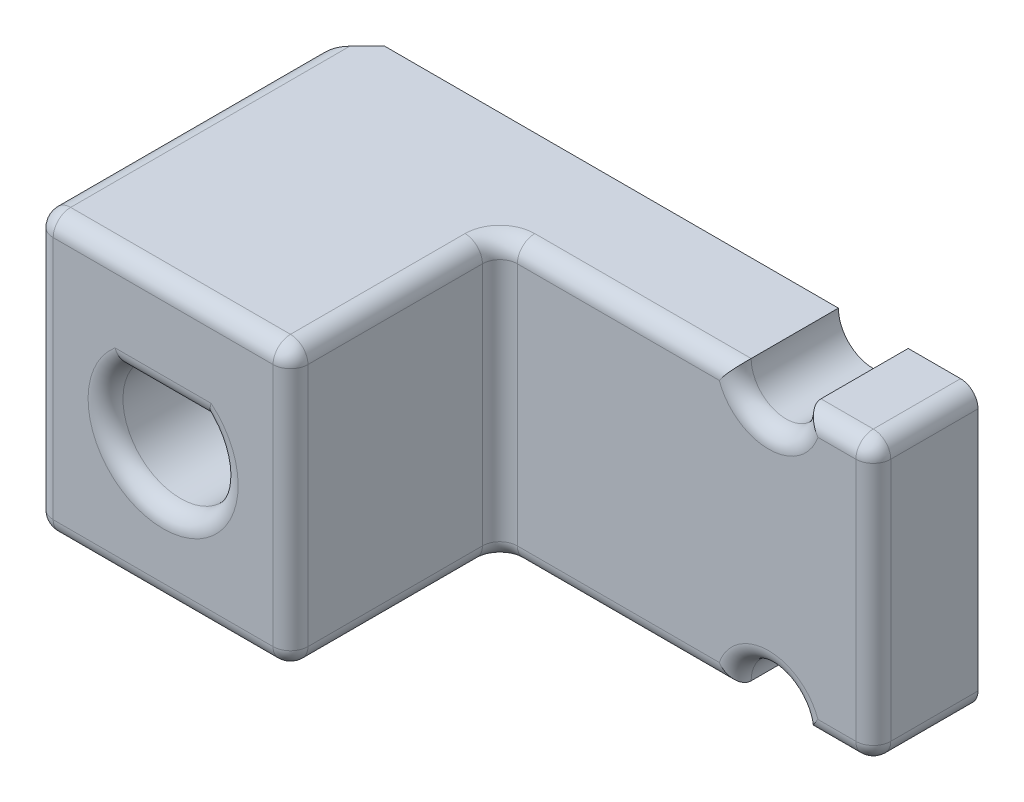
SolidWorks part; units mm, degrees
note: The reader was unsure of these and kept them because the rebuilt part matched: shared geometry of "Sketch1<3>".
ref_plane "Front Plane" through (0, 0, 0) normal (0, 0, 1) x (1, 0, 0)
ref_plane "Top Plane" through (0, 0, 0) normal (0, 1, 0) x (1, 0, 0)
ref_plane "Right Plane" through (0, 0, 0) normal (1, 0, 0) x (0, 0, -1)
sketch "Sketch1" plane through (0, 0, 0) normal (0, 0, 1) x (1, 0, 0)
  line L0 (-1.1832, 1.15) -> (1.1832, 1.15)
  line L2 (-3.65, -4) -> (3.65, -4)
  line L3 (-3.65, -4) -> (-3.65, 4)
  line L4 (-3.65, 4) -> (3.65, 4)
  line L5 (3.65, -4) -> (3.65, 4)
  circle A0 centre (0, 0) radius 1.65
  point P5 (0, -1.65)
  point P10 (-1.65, 0)
  point P11 (1.65, 0)
  point P12 (0, -1.65)
  point P13 (0, 1.65)
  dimension "D1" = 3.3
  dimension "D3" = 2
  dimension "D2" = 2.8
  dimension "D4" = 2
  dimension "D5" = 4
  dimension "D6" = 4
extrude "Boss-Extrude1" add sketch "Sketch1" along normal blind 5
extrude "Boss-Extrude2" add sketch "Sketch1<3>" against normal blind 1
sketch "Sketch1<3>" plane through (0, 0, 0) normal (0, 0, 1) x (1, 0, 0) same geometry as "Sketch1"
sketch "Sketch2" plane through (0, 0, -1) normal (0, 0, -1) x (-1, 0, 0)
  line L0 (3.65, -4) -> (3.65, 4) construction
  line L1 (3.65, 4) -> (-11.35, 4)
  line L2 (3.65, 4) -> (3.65, -4)
  line L3 (3.65, -4) -> (-11.35, -4)
  line L4 (-11.35, 4) -> (-11.35, -4)
  line L5 (-11.35, 4) -> (-14.35, 4)
  line L6 (-11.35, 4) -> (-11.35, -4)
  line L7 (-11.35, -4) -> (-14.35, -4)
  line L8 (-14.35, 4) -> (-14.35, -4)
  arc A0 (-10.35, -4) -> (-12.35, -4) centre (-11.35, -4) ccw
  arc A2 (-10.35, 4) -> (-12.35, 4) centre (-11.35, 4) cw
  dimension "D4" = 1
  dimension "D1" = 4
  dimension "D2" = 4
  dimension "D3" = 15
  dimension "D5" = 2
extrude "Boss-Extrude3" add sketch "Sketch2" along normal blind 3
chamfer "Chamfer1" distance 1 angle 45 1 edges at (-3.65, 0, -4)
fillet "Fillet1" radius 0.5 20 edges at (13.35, 4, -1) (11.35, 3, -1) (14.35, 4, -2.5) (14.35, -4, -2.5) (14.35, 0, -1) (13.35, -4, -1) (0, -1.65, 5) (0, 1.15, 5) (0, 4, 5) (-3.65, 4, 1) (-3.65, -4, 1) (3.65, 0, 5) (0, -4, 5) (-3.65, 0, 5) (11.35, -3, -1)
